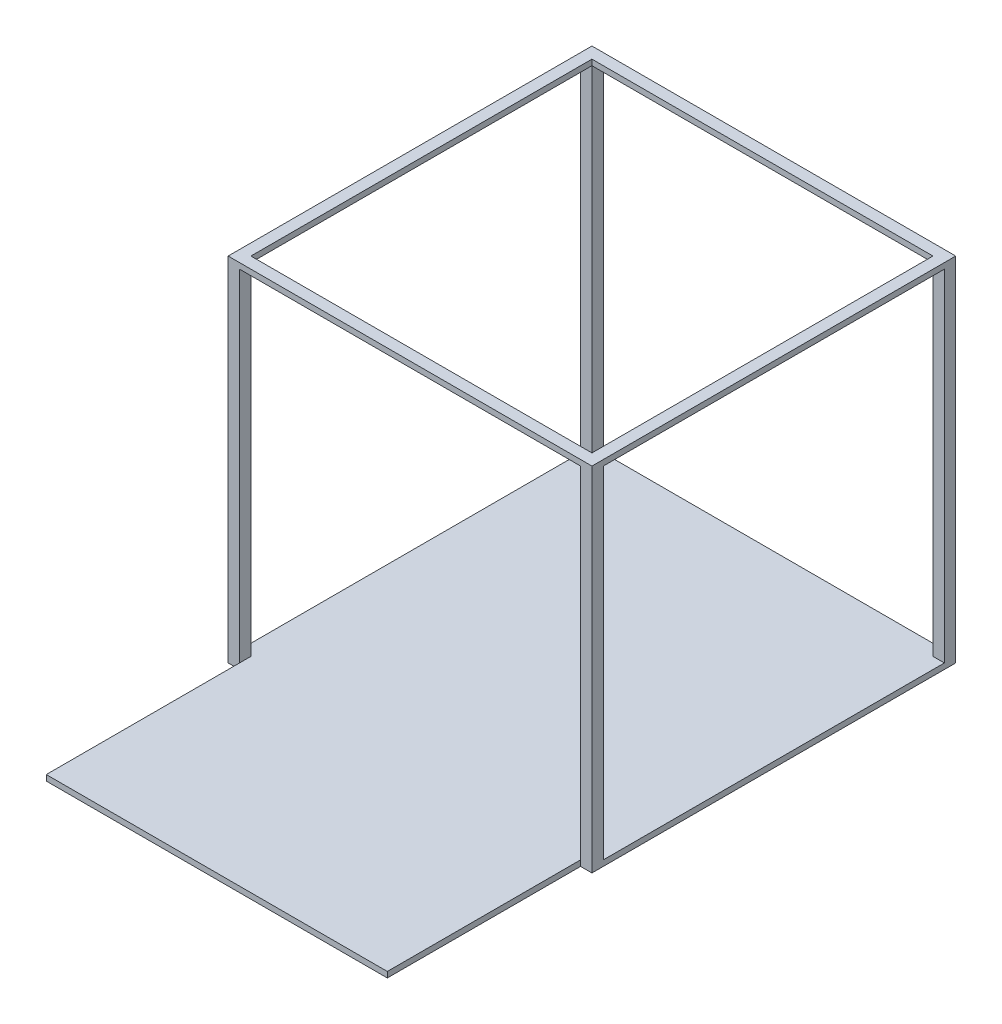
SolidWorks part; units mm, degrees
ref_plane "Front Plane" through (0, 0, 0) normal (0, 0, 1) x (1, 0, 0)
ref_plane "Top Plane" through (0, 0, 0) normal (0, 1, 0) x (1, 0, 0)
ref_plane "Right Plane" through (0, 0, 0) normal (1, 0, 0) x (0, 0, -1)
sketch "Sketch1" plane through (0, 0, 0) normal (0, 1, 0) x (1, 0, 0)
  line L1 (-203.2, -203.2) -> (203.2, -203.2)
  line L2 (-203.2, -203.2) -> (-203.2, 203.2)
  line L3 (-203.2, 203.2) -> (203.2, 203.2)
  line L4 (203.2, -203.2) -> (203.2, 203.2)
  line L5 (-203.2, -203.2) -> (203.2, 203.2) construction
  line L6 (-203.2, 203.2) -> (203.2, -203.2) construction
  point P0 (0, 0)
  dimension "D1" = 406.4
  dimension "D2" = 406.4
extrude "Boss-Extrude1" add sketch "Sketch1" along normal blind 6.35
sketch "Sketch2" plane through (0, 6.35, 0) normal (0, 1, 0) x (1, 0, 0)
  line L0 (0, 203.2) -> (0, -203.2) construction
  line L1 (-203.2, 203.2) -> (-190.5, 203.2)
  line L2 (-203.2, 203.2) -> (-203.2, 190.5)
  line L3 (-203.2, 190.5) -> (-190.5, 190.5)
  line L4 (-190.5, 203.2) -> (-190.5, 190.5)
  line L5 (203.2, 203.2) -> (-203.2, 203.2) construction
  line L6 (-203.2, -203.2) -> (203.2, -203.2) construction
  line L7 (-203.2, 0) -> (203.2, 0) construction
  line L8 (-203.2, 203.2) -> (-203.2, -203.2) construction
  line L9 (203.2, -203.2) -> (203.2, 203.2) construction
  line L10 (190.5, 203.2) -> (190.5, 190.5)
  line L11 (203.2, 190.5) -> (190.5, 190.5)
  line L12 (203.2, 203.2) -> (203.2, 190.5)
  line L13 (203.2, 203.2) -> (190.5, 203.2)
  line L14 (203.2, -203.2) -> (190.5, -203.2)
  line L15 (203.2, -203.2) -> (203.2, -190.5)
  line L16 (203.2, -190.5) -> (190.5, -190.5)
  line L17 (190.5, -203.2) -> (190.5, -190.5)
  line L18 (-190.5, -203.2) -> (-190.5, -190.5)
  line L19 (-203.2, -190.5) -> (-190.5, -190.5)
  line L20 (-203.2, -203.2) -> (-203.2, -190.5)
  line L21 (-203.2, -203.2) -> (-190.5, -203.2)
  dimension "D1" = 12.7
  dimension "D2" = 12.7
extrude "Boss-Extrude2" add sketch "Sketch2" along normal blind 381
sketch "Sketch3" plane through (0, 387.35, 0) normal (0, 1, 0) x (1, 0, 0)
  line L0 (203.2, -190.5) -> (190.5, -190.5) construction
  line L1 (-203.2, 203.2) -> (203.2, 203.2)
  line L2 (-203.2, 203.2) -> (-203.2, -203.2)
  line L3 (-203.2, -203.2) -> (203.2, -203.2)
  line L4 (203.2, 203.2) -> (203.2, -203.2)
  line L5 (-190.5, 190.5) -> (190.5, 190.5)
  line L6 (-190.5, 190.5) -> (-190.5, -190.5)
  line L7 (-190.5, -190.5) -> (190.5, -190.5)
  line L8 (190.5, 190.5) -> (190.5, -190.5)
  line L9 (190.5, -190.5) -> (190.5, -203.2) construction
extrude "Boss-Extrude3" add sketch "Sketch3" along normal blind 6.35
sketch "Sketch4" plane through (0, 6.35, 0) normal (0, 1, 0) x (1, 0, 0)
  line L0 (190.5, -190.5) -> (190.5, -203.2) construction
  line L1 (-190.5, -190.5) -> (190.5, -190.5)
  line L2 (-190.5, -190.5) -> (-190.5, -419.1)
  line L3 (-190.5, -419.1) -> (190.5, -419.1)
  line L4 (190.5, -190.5) -> (190.5, -419.1)
  line L5 (-203.2, 190.5) -> (-190.5, 190.5) construction
  dimension "D1" = 609.6
extrude "Boss-Extrude4" add sketch "Sketch4" against normal blind 6.35
ref_plane "Plane1" through (0, 793.75, 0) normal (0, 1, 0) x (1, 0, 0)
sketch "Sketch5" plane through (0, 793.75, 0) normal (0, 1, 0) x (1, 0, 0)
  line L0 (-190.5, -419.1) -> (190.5, -419.1) construction
  line L1 (-203.2, 203.2) -> (203.2, 203.2)
  line L2 (-203.2, 203.2) -> (-203.2, -431.8)
  line L3 (-203.2, -431.8) -> (203.2, -431.8)
  line L4 (203.2, 203.2) -> (203.2, -431.8)
  line L6 (-190.5, 190.5) -> (190.5, 190.5)
  line L7 (-190.5, 190.5) -> (-190.5, -419.1)
  line L8 (-190.5, -419.1) -> (190.5, -419.1)
  line L9 (190.5, 190.5) -> (190.5, -419.1)
  dimension "D1" = 12.7
extrude "Boss-Extrude5" [suppressed] add sketch "Sketch5" along normal blind 6.35 separate body
sketch "Sketch6" plane through (0, 0, 419.1) normal (0, 0, 1) x (1, 0, 0)
  line L1 (-190.5, 0) -> (190.5, 0)
  line L2 (-190.5, 0) -> (-190.5, 387.35)
  line L3 (-190.5, 387.35) -> (190.5, 387.35)
  line L4 (190.5, 0) -> (190.5, 387.35)
extrude "Boss-Extrude6" [suppressed] add sketch "Sketch6" along normal blind 3.175
